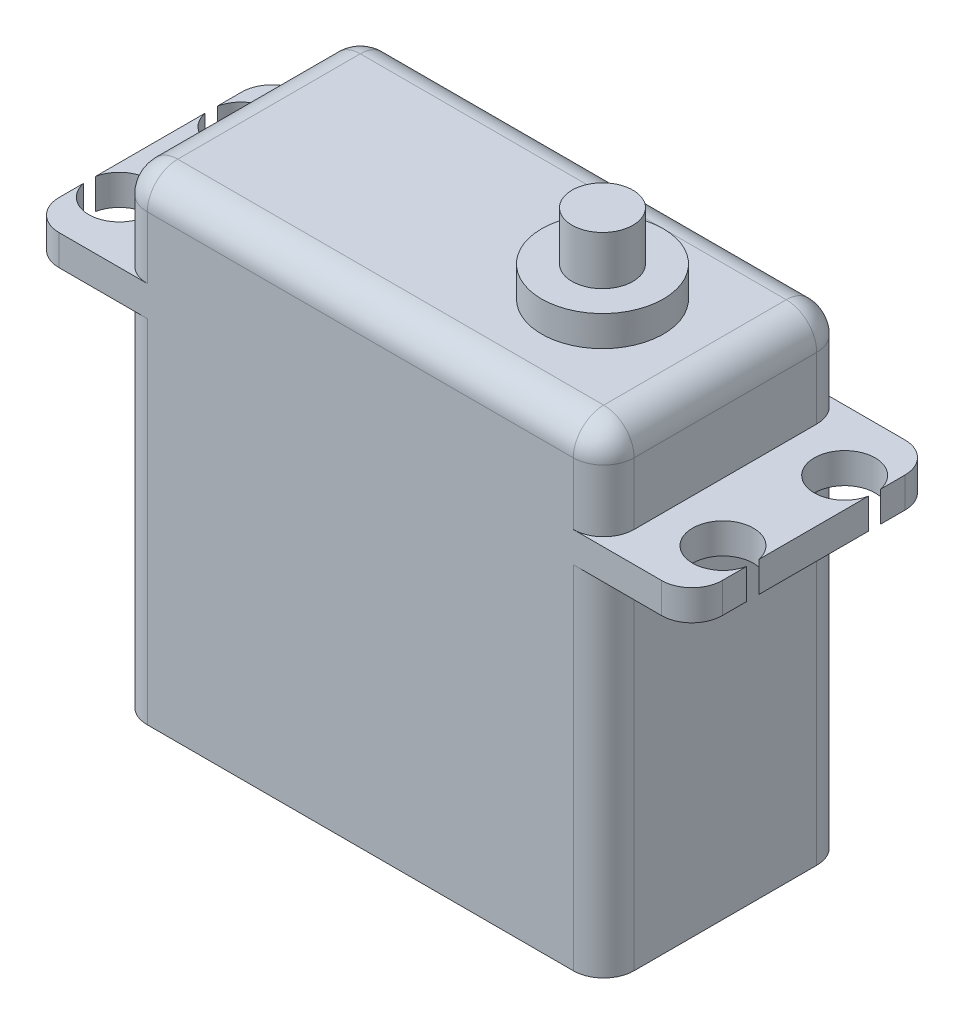
SolidWorks part; units mm, degrees
ref_plane "Front Plane" through (0, 0, 0) normal (0, 0, 1) x (1, 0, 0)
ref_plane "Top Plane" through (0, 0, 0) normal (0, 1, 0) x (1, 0, 0)
ref_plane "Right Plane" through (0, 0, 0) normal (1, 0, 0) x (0, 0, -1)
sketch "Sketch1" plane through (0, 0, 0) normal (0, 1, 0) x (1, 0, 0)
  line L1 (0, 0) -> (40, 0)
  line L2 (0, 0) -> (0, 20)
  line L3 (0, 20) -> (40, 20)
  line L4 (40, 0) -> (40, 20)
  dimension "D1" = 40
  dimension "D2" = 20
extrude "Boss-Extrude1" add sketch "Sketch1" along normal blind 39
ref_plane "Plane1" through (0, 28.9, 0) normal (0, -1, 0) x (-1, 0, 0)
sketch "Sketch2" plane through (0, 28.9, 0) normal (0, -1, 0) x (-1, 0, 0)
  line L1 (-47.25, 20) -> (7.25, 20)
  line L2 (-47.25, 20) -> (-47.25, 0)
  line L3 (-47.25, 0) -> (7.25, 0)
  line L4 (7.25, 20) -> (7.25, 0)
  line L5 (-40, 20) -> (0, 20) construction
  line L7 (0, 0) -> (-40, 0) construction
  line L8 (-44.8, 15) -> (-44.8, 5) construction
  circle A0 centre (-44.8, 15) radius 2.5
  circle A1 centre (-44.8, 5) radius 2.5
  circle A2 centre (4.8, 15) radius 2.5
  circle A3 centre (4.8, 5) radius 2.5
  point P6 (-20, 0)
  point P8 (-20, 20)
  point P18 (-44.8, 10)
  point P19 (-47.25, 10)
  dimension "D2" = 5
  dimension "D1" = 54.5
  dimension "D3" = 49.6
  dimension "D4" = 10
  dimension "D5" = 2.45
extrude "Boss-Extrude2" add sketch "Sketch2" against normal blind 2.5 contours L8 A0 L2 A1 | A0 L8 A1 L2 L3 L4 A3 A2 L1 region at (19.6142, 28.9, -10) region at (46.1372, 28.9, -10)
fillet "Fillet1" radius 2.5 4 edges at (-7.25, 30.15, 0) (-7.25, 30.15, -20) (47.25, 30.15, -20) (47.25, 30.15, 0)
sketch "Sketch3" plane through (0, 39, 0) normal (0, 1, 0) x (1, 0, 0)
  line L0 (47.25, 14.5025) -> (47.25, 5.4975) construction
  circle A0 centre (29.9, 10) radius 5
  arc A1 (47.25, 15.4975) -> (47.25, 14.5025) centre (44.8, 15) ccw construction
  point P2 (47.25, 10)
  dimension "D1" = 10
  dimension "D2" = 14.9
extrude "Boss-Extrude3" add sketch "Sketch3" along normal blind 2.5
sketch "Sketch4" plane through (0, 41.5, 0) normal (0, 1, 0) x (1, 0, 0)
  circle A0 centre (29.9, 10) radius 2.5
  circle A1 centre (29.9, 10) radius 5 construction
  dimension "D1" = 5
extrude "Boss-Extrude4" add sketch "Sketch4" along normal blind 4
fillet "Fillet2" radius 2.5 10 edges at (20, 39, 0) (20, 39, -20) (0, 35.2, -20) (0, 14.45, -20) (40, 14.45, -20) (40, 35.2, -20) (0, 35.2, 0) (0, 14.45, 0) (40, 14.45, 0) (40, 35.2, 0)
fillet "Fillet3" radius 2.5 6 edges at (0.7322, 38.2678, -19.2678) (0.7322, 38.2678, -0.7322) (39.2678, 38.2678, -0.7322) (39.2678, 38.2678, -19.2678) (0, 39, -10) (40, 39, -10)
